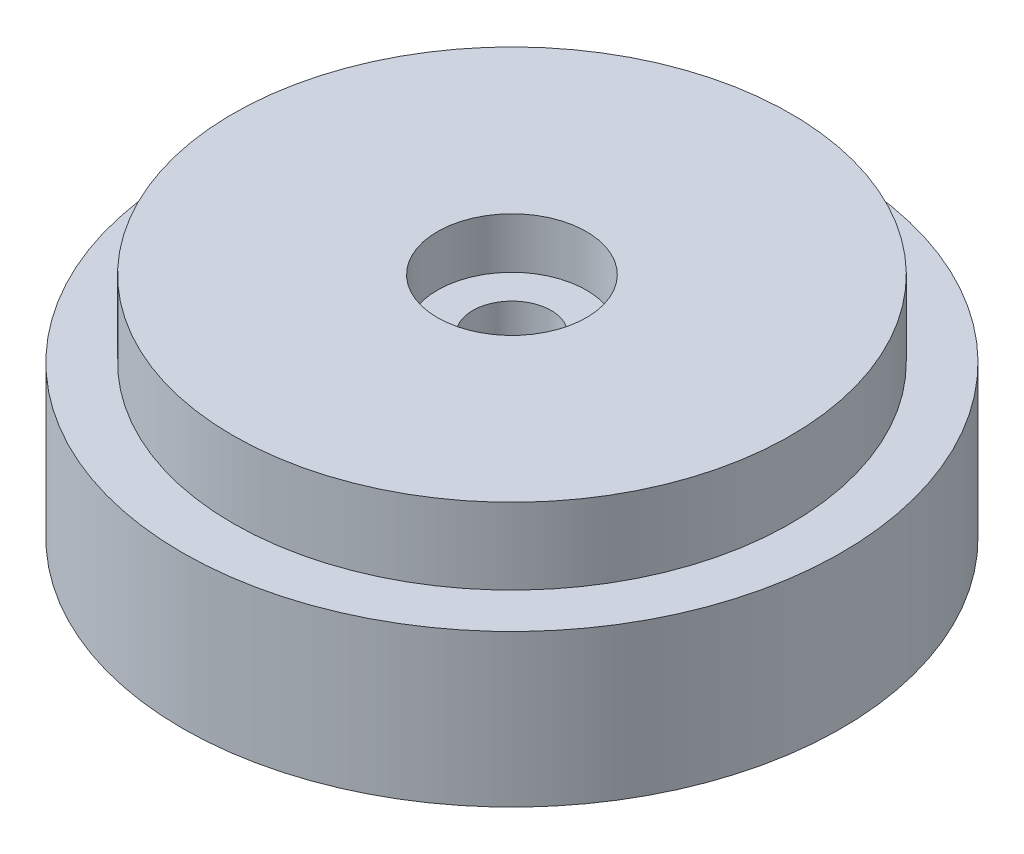
SolidWorks part; units mm, degrees
ref_plane "Front Plane" through (0, 0, 0) normal (0, 0, 1) x (1, 0, 0)
ref_plane "Top Plane" through (0, 0, 0) normal (0, 1, 0) x (1, 0, 0)
ref_plane "Right Plane" through (0, 0, 0) normal (1, 0, 0) x (0, 0, -1)
sketch "Sketch2" plane through (0, 0, 0) normal (0, 1, 0) x (1, 0, 0)
  line L0 (5, 5) -> (-5, -5) construction
  line L1 (-5, 5) -> (5, -5) construction
  circle A0 centre (0, 0) radius 11
  circle A10 centre (-5, 5) radius 3.05
  circle A11 centre (5, 5) radius 3.05
  circle A12 centre (5, -5) radius 3.05
  circle A13 centre (-5, -5) radius 3.05
  circle A14 centre (0, 0) radius 2.94
  circle A15 centre (0, 0) radius 1.55
  circle A16 centre (0, 0) radius 13
  dimension "D1" = 22
  dimension "D2" = 6.1
  dimension "D3" = 26
  dimension "D7" = 3.1
  dimension "D8" = 5.88
  dimension "D4" = 10
extrude "Boss-Extrude1" add sketch "Sketch2" along normal blind 9 contours A0 A14 A13 A12 A11 A10 | A12 | A11 | A10 | A13 region at (-10.6889, 0, 0) region at (-5, 0, -5) region at (5, 0, -5) region at (5, 0, 5) region at (-5, 0, 5)
extrude "Boss-Extrude2" add sketch "Sketch2<3>" along normal blind 7 contours A14 A15 region at (-2.8568, 0, 0)
sketch "Sketch2<3>" plane through (0, 0, 0) normal (0, 1, 0) x (1, 0, 0) same geometry as "Sketch2"
extrude "Cut-Extrude1" cut sketch "Sketch2<4>" along normal blind 3 contours A14 A15 region at (-2.8568, 0, 0)
sketch "Sketch2<4>" plane through (0, 0, 0) normal (0, 1, 0) x (1, 0, 0) same geometry as "Sketch2"
extrude "Cut-Extrude2" cut sketch "Sketch2<6>" along normal blind 8.6 contours A11 | A12 | A13 | A10 region at (-5, 0, -5) region at (5, 0, -5) region at (5, 0, 5) region at (-5, 0, 5)
sketch "Sketch2<6>" plane through (0, 0, 0) normal (0, 1, 0) x (1, 0, 0) same geometry as "Sketch2"
extrude "Boss-Extrude3" add sketch "Sketch2<7>" along normal blind 6 contours A16 A0 region at (-12.6323, 0, 0)
sketch "Sketch2<7>" plane through (0, 0, 0) normal (0, 1, 0) x (1, 0, 0) same geometry as "Sketch2"
